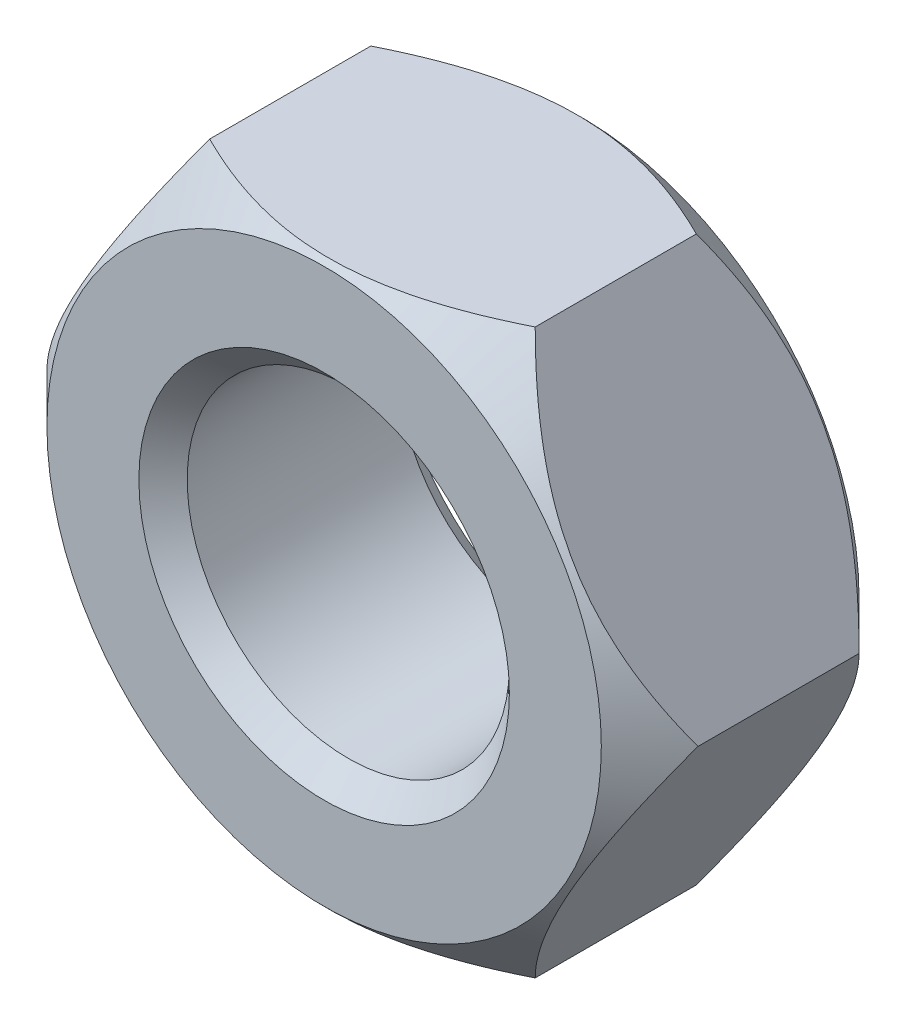
SolidWorks part; units mm, degrees
ref_plane "Front Plane" through (0, 0, 0) normal (0, 0, 1) x (1, 0, 0)
ref_plane "Top Plane" through (0, 0, 0) normal (0, 1, 0) x (1, 0, 0)
ref_plane "Right Plane" through (0, 0, 0) normal (1, 0, 0) x (0, 0, -1)
sketch "Sketch1" plane through (0, 0, 0) normal (0, 0, 1) x (1, 0, 0)
  line L1 (2.0207, 3.5) -> (-2.0207, 3.5) construction
  line L2 (-2.0207, 3.5) -> (-4.0415, 0) construction
  line L3 (-4.0415, 0) -> (-2.0207, -3.5) construction
  line L4 (-2.0207, -3.5) -> (2.0207, -3.5) construction
  line L5 (2.0207, -3.5) -> (4.0415, 0) construction
  line L6 (4.0415, 0) -> (2.0207, 3.5) construction
  circle A0 centre (0, 0) radius 4.0415
  circle A1 centre (0, 0) radius 3.5 construction
  dimension "D1" = 7
extrude "Boss-Extrude1" add sketch "Sketch1" along normal mid plane 3.2
chamfer "Chamfer1" distance 0.6 angle 45 2 edges at (4.0415, 0, 1.6) (4.0415, 0, -1.6)
sketch "Sketch2" plane through (0, 0, 1.6) normal (0, 0, 1) x (1, 0, 0)
  line L1 (2.0207, 3.5) -> (-2.0207, 3.5)
  line L2 (-2.0207, 3.5) -> (-4.0415, 0)
  line L3 (-4.0415, 0) -> (-2.0207, -3.5)
  line L4 (-2.0207, -3.5) -> (2.0207, -3.5)
  line L5 (2.0207, -3.5) -> (4.0415, 0)
  line L6 (4.0415, 0) -> (2.0207, 3.5)
  circle A0 centre (0, 0) radius 3.5 construction
  circle A1 centre (0, 0) radius 4.0415 construction
  circle A2 centre (0, 0) radius 4.0415
  circle A3 centre (0, 0) radius 2
  circle M2 centre (0, 0) radius 3.4415
  dimension "D1" = 4
extrude "Cut-Extrude1" cut sketch "Sketch2" against normal through all contours L1 A2 M2 | L2 A2 M2 | L3 A2 M2 | L4 A2 M2 | L5 A2 M2 | L6 A2 M2 | A3 region at (3.2198, 1.8589, 1.6) region at (0, 3.7179, 1.6) region at (-3.2198, 1.8589, 1.6) region at (3.2198, -1.8589, 1.6) region at (-3.2198, -1.8589, 1.6) region at (0, -3.7179, 1.6) region at (0, 0, 1.6)
chamfer "Chamfer2" distance 0.3 angle 45 2 edges at (2, 0, 1.6) (2, 0, -1.6)
